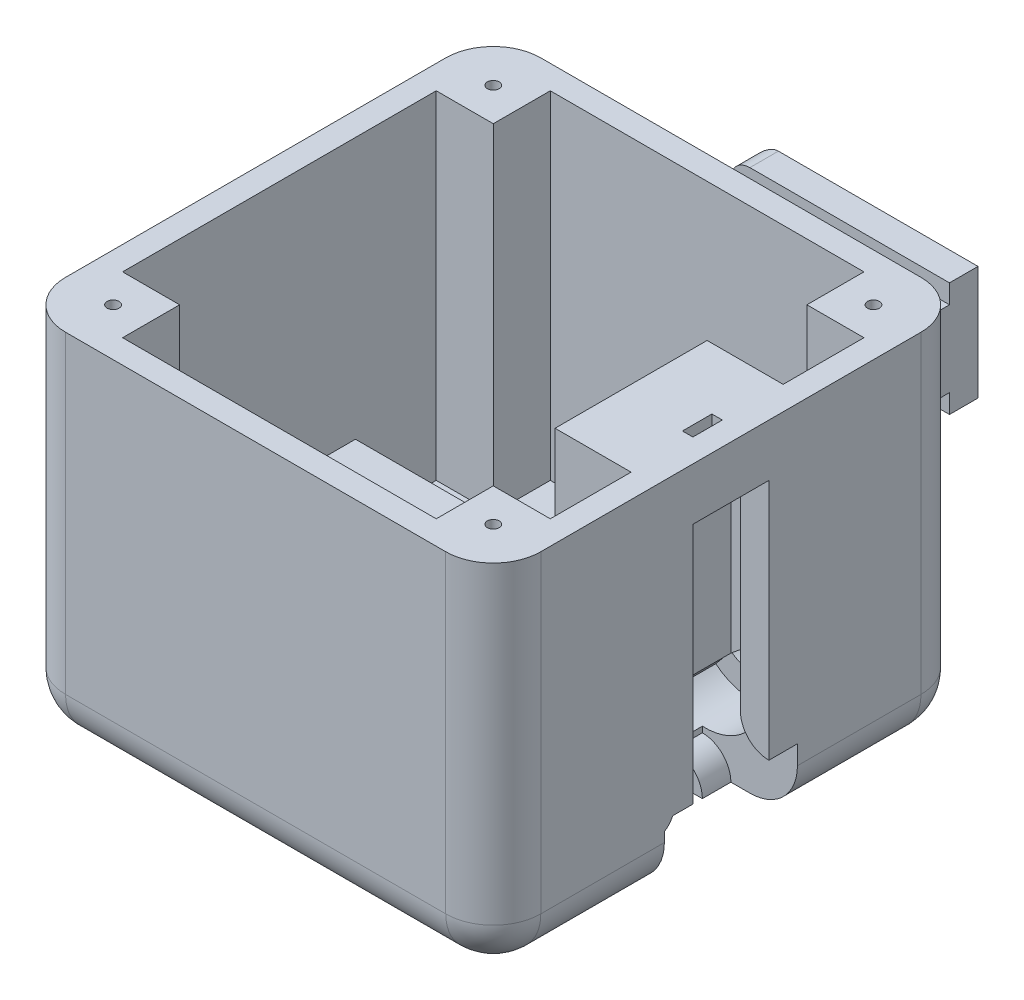
SolidWorks part; units mm, degrees
ref_plane "Front Plane" through (0, 0, 0) normal (0, 0, 1) x (1, 0, 0)
ref_plane "Top Plane" through (0, 0, 0) normal (0, 1, 0) x (1, 0, 0)
ref_plane "Right Plane" through (0, 0, 0) normal (1, 0, 0) x (0, 0, -1)
sketch "Sketch1" plane through (0, 0, 0) normal (0, 1, 0) x (1, 0, 0)
  line L1 (25, 25) -> (-25, 25)
  line L2 (25, 25) -> (25, -25)
  line L3 (25, -25) -> (-25, -25)
  line L4 (-25, 25) -> (-25, -25)
  line L5 (25, 25) -> (-25, -25) construction
  line L6 (25, -25) -> (-25, 25) construction
  point P0 (0, 0)
  dimension "D1" = 50
  dimension "D2" = 50
extrude "Boss-Extrude1" add sketch "Sketch1" along normal blind 38
shell "Shell1" thickness 2.5 removed face at (0, 38, 0)
sketch "Sketch2" plane through (0, 2.5, 0) normal (0, 1, 0) x (1, 0, 0)
  line L2 (9.676, 17.0496) -> (9.676, 13.5) construction
  line L3 (-10.3, -16.9504) -> (-10.324, -16.9504) construction
  line L4 (-10.324, 9.8396) -> (-10.324, -13.6) construction
  line L5 (-10.3, 6.5) -> (-10.324, 6.5)
  line L13 (10.3, 13.5) -> (10.3, 22.5)
  line L14 (22.5, 7.28) -> (22.5, 22.5)
  line L15 (10.3, 7.28) -> (22.5, 7.28)
  line L16 (10.3, 7.28) -> (10.3, 13.5)
  line L17 (10.3, 13.5) -> (9.676, 13.5)
  line L19 (22.5, 22.5) -> (10.3, 22.5)
  line L28 (-10.3, -13.6) -> (-10.324, -13.6)
  line L29 (-10.3, -16.9504) -> (-10.3, -20.79)
  line L35 (9.676, -16.9504) -> (-10.3, -16.9504) construction
  line L40 (22.5, -22.5) -> (22.5, 22.5) construction
  point P0 (0, 0)
  line M21 (22.5, -22.5) -> (22.5, 22.5)
  line M22 (22.5, 22.5) -> (-22.5, 22.5)
  dimension "D7" = 9
sketch "Sketch3" plane through (0, 2.5, 0) normal (0, 1, 0) x (1, 0, 0)
  line L0 (22.5, -8) -> (22.5, 8)
  line L1 (22.5, -22.5) -> (22.5, 22.5) construction
  line L2 (22.5, 8) -> (22.5, -8)
  line L3 (22.5, 8) -> (-22.5, 8)
  line L4 (22.5, -8) -> (-22.5, -8)
  line L5 (-22.5, 8) -> (-22.5, -8)
  line L6 (-22.5, 22.5) -> (-22.5, -22.5) construction
  point P4 (22.5, 0)
  point P6 (22.5, 0)
  line M6 (-22.5, 22.5) -> (-22.5, -22.5)
  line M8 (22.5, -22.5) -> (22.5, 22.5)
  dimension "D1" = 16
extrude "Boss-Extrude2" add sketch "Sketch2" along normal blind 21 contours L16 L15 L13 M21 M22
extrude "Boss-Extrude3" add sketch "Sketch3" along normal blind 8 contours L4 L3 M8 M6
sketch "Sketch4" plane through (0, 0, 0) normal (0, -1, 0) x (1, 0, 0)
  line L4 (25, -4) -> (-7.5, -4)
  line L5 (22.5, -8) -> (25, -8) construction
  line L6 (22.5, 8) -> (25, 8) construction
  line L7 (22.5, 0) -> (25, 0)
  line L8 (25, 25) -> (25, -25) construction
  line L9 (-7.5, -4) -> (-7.5, 4)
  line L10 (-7.5, 4) -> (25, 4)
  line L11 (25, 4) -> (25, -4)
  point P10 (25, 0)
  dimension "D1" = 8
  dimension "D2" = 32.5
extrude "Cut-Extrude1" cut sketch "Sketch4" against normal blind 3
ref_plane "Plane1" through (0, 3, 0) normal (0, -1, 0) x (-1, 0, 0)
sketch "Sketch7" plane through (0, 3, 0) normal (0, -1, 0) x (-1, 0, 0)
  line L5 (-25, 4) -> (-25, -4) construction
  line L6 (-25, -6) -> (-25, 6)
  line L7 (-25, -6) -> (7.5, -6)
  line L8 (-25, 6) -> (7.5, 6)
  line L9 (7.5, -6) -> (7.5, 6)
  line L10 (-25, -25) -> (-25, -4) construction
  line L11 (-25, 4) -> (-25, 25) construction
  point P4 (-25, 0)
  point P11 (-25, 0)
  dimension "D1" = 12
  dimension "D2" = 32.5
extrude "Cut-Extrude2" cut sketch "Sketch7" against normal blind 3
sketch "Sketch8" plane through (22.5, 0, 0) normal (-1, 0, 0) x (0, 0, 1)
  line L0 (-8, 10.5) -> (-8, 38)
  line L1 (22.5, 38) -> (-22.5, 38) construction
  line L2 (8, 10.5) -> (8, 38)
  line L3 (8, 38) -> (-8, 38)
  line L4 (-8, 10.5) -> (8, 10.5)
extrude "Boss-Extrude4" add sketch "Sketch8" along normal blind 8
sketch "Sketch9" plane through (25, 0, 0) normal (1, 0, 0) x (0, 0, -1)
  line L0 (-4, 0) -> (-4, 32.5)
  line L2 (4, 0) -> (4, 32.5)
  line L3 (4, 32.5) -> (-4, 32.5)
  line L4 (-4, 0) -> (4, 0)
  dimension "D1" = 32.5
extrude "Cut-Extrude3" cut sketch "Sketch9" against normal blind 3 contours L4 L2 L3 L0
ref_plane "Plane2" through (22, 0, 0) normal (1, 0, 0) x (0, 0, -1)
sketch "Sketch10" plane through (22, 0, 0) normal (1, 0, 0) x (0, 0, -1)
  line L0 (-6, 0) -> (-6, 32.5)
  line L1 (-25, 0) -> (-4, 0) construction
  line L3 (6, 3) -> (6, 0)
  line L4 (4, 0) -> (25, 0) construction
  line L5 (6, 0) -> (6, 32.5)
  line L7 (6, 32.5) -> (-6, 32.5)
  line L8 (-6, 0) -> (6, 0)
  dimension "D1" = 32.5
extrude "Cut-Extrude5" cut sketch "Sketch10" against normal blind 3 contours L0 L8 L3 L5 L7
ref_plane "Plane3" through (0, 0, 4) normal (0, 0, -1) x (-1, 0, 0)
sketch "Sketch13" plane through (0, 0, 4) normal (0, 0, -1) x (-1, 0, 0)
  line L0 (-25, 0) -> (-22, 0)
  line L1 (-25, 0) -> (-25, 3.0115)
  line L2 (-22, 0) -> (-22, 3.0115)
  line L3 (-25, 3.0115) -> (-22, 3.0115)
extrude "Cut-Extrude7" cut sketch "Sketch13" against normal blind 2 and the other way blind 10
ref_plane "Plane4" through (0, 0, 6) normal (0, 0, -1) x (-1, 0, 0)
fillet "Fillet1" radius 5 9 edges at (-25, 19, 25) (25, 19, 25) (25, 19, -25) (-25, 19, -25) (-25, 0, 0) (0, 0, 25) (25, 0, 15.5) (0, 0, -25) (25, 0, -15.5)
ref_plane "Plane6" through (0, 0, 1.5) normal (0, 0, -1) x (-1, 0, 0)
sketch "Sketch16" plane through (0, 0, 1.5) normal (0, 0, -1) x (-1, 0, 0)
  line L0 (-25, 9.7) -> (-25, 0) construction
  line L1 (-17.1, 9.7) -> (-15.3, 9.7) construction
  line L2 (-25, 0) -> (-15.3, 0) construction
  line L3 (-15.3, 9.7) -> (-15.3, 7.9) construction
  line L5 (-15.3, 7.9) -> (-15.3, 0) construction
  line L6 (-25, 9.7) -> (-17.1, 9.7) construction
  circle A0 centre (-15.3, 9.7) radius 1.8
  dimension "D3" = 3.6
  dimension "D1" = 9.7
  dimension "D2" = 9.7
extrude "Cut-Extrude8" cut sketch "Sketch16" along normal through all
sketch "Sketch17" plane through (0, 0, -25) normal (0, 0, -1) x (-1, 0, 0)
  line L0 (-20, 36) -> (3, 36)
  line L1 (-20, 38) -> (-20, 5) construction
  line L2 (3, 36) -> (3, 24)
  line L3 (3, 24) -> (-20, 24)
  line L4 (-20, 24) -> (-20, 36)
  line L5 (-20, 38) -> (20, 38) construction
  dimension "D1" = 12
  dimension "D2" = 23
  dimension "D3" = 2
extrude "Boss-Extrude5" add sketch "Sketch17" along normal blind 6
sketch "Sketch18" plane through (-3, 0, 0) normal (-1, 0, 0) x (0, 0, 1)
  line L0 (-31, 30) -> (-25, 30) construction
  line L1 (-31, 24) -> (-31, 36) construction
  line L2 (-25, 24) -> (-25, 36) construction
  line L3 (-28, 24) -> (-25, 24)
  line L4 (-28, 24) -> (-28, 26)
  line L5 (-25, 24) -> (-25, 26)
  line L6 (-28, 26) -> (-25, 26)
  line L7 (-31, 24) -> (-25, 24) construction
  line L8 (-25, 36) -> (-25, 34)
  line L9 (-28, 34) -> (-25, 34)
  line L10 (-28, 36) -> (-28, 34)
  line L11 (-28, 36) -> (-25, 36)
  dimension "D1" = 4
extrude "Cut-Extrude9" cut sketch "Sketch18" against normal through all
ref_plane "Plane5" through (0, 0, -25) normal (0, 0, -1) x (-1, 0, 0)
sketch "Sketch20" plane through (0, 0, 4) normal (0, 0, -1) x (-1, 0, 0)
  line L0 (-22, 6) -> (-22, 32.5) construction
  line L2 (-22, 10) -> (-22, 7)
  line L7 (-22, 6) -> (-25, 6) construction
  line L8 (-24, 6) -> (-22, 6)
  line L9 (-22, 6) -> (-22, 7)
  line L10 (-24, 6) -> (-25, 6)
  line L11 (-25, 6) -> (-25, 7)
  line L12 (-25, 6) -> (-25, 32.5) construction
  arc A0 (-25, 7) -> (-22, 10) centre (-25, 10) ccw
  dimension "D1" = 1
  dimension "D2" = 3
extrude "Cut-Extrude12" cut sketch "Sketch20" against normal blind 2
sketch "Sketch21" plane through (0, 0, 4) normal (0, 0, -1) x (-1, 0, 0)
  line L4 (-19, 3) -> (-19, 0)
  line L5 (-19, 0) -> (-18, 0)
  line L6 (7.5, 0) -> (-19, 0) construction
  line L7 (-19, 3) -> (-15, 3)
  line L8 (7.5, 3) -> (-19, 3) construction
  arc A3 (-18, 0) -> (-15, 3) centre (-15, 0) cw
  dimension "D1" = 4
  dimension "D2" = 1
extrude "Cut-Extrude13" cut sketch "Sketch21" against normal blind 2
sketch "Sketch22" plane through (0, 0, 4) normal (0, 0, -1) x (-1, 0, 0)
  line L1 (-15.3, 9.7) -> (-11.4116, 5)
  line L2 (-19, 6) -> (7.5, 6) construction
  line L3 (-15.3, 9.7) -> (-20, 13.5884)
  line L4 (-19, 6) -> (-19, 32.5) construction
  arc A0 (-20, 13.5884) -> (-11.4116, 5) centre (-15.3, 9.7) ccw
  arc A1 (-11.4116, 5) -> (-20, 13.5884) centre (-15.3, 9.7) ccw construction
  dimension "D1" = 12.2
  dimension "D2" = 1
  dimension "D3" = 1
extrude "Cut-Extrude14" cut sketch "Sketch22" along normal blind 16
sketch "Sketch19" plane through (0, 0, -25) normal (0, 0, -1) x (-1, 0, 0)
  line L5 (-29.1876, 23.5876) -> (-2.7229, -2.8771) construction
  line L6 (-8.2477, 16.7523) -> (-36.3257, -11.3257) construction
  line L18 (-13.6992, 10.523) -> (-13.1688, 11.0533)
  line L19 (-13.1688, 11.0533) -> (-13.9467, 11.8312)
  line L20 (-13.9467, 11.8312) -> (-14.477, 11.3008)
  line L21 (-17.4312, 8.3467) -> (-16.9008, 8.877)
  line L22 (-16.6533, 7.5688) -> (-17.4312, 8.3467)
  line L23 (-16.123, 8.0992) -> (-16.6533, 7.5688)
  arc A4 (-13.6992, 10.523) -> (-14.477, 11.3008) centre (-15.3, 9.7) ccw
  arc A5 (-16.123, 8.0992) -> (-16.9008, 8.877) centre (-15.3, 9.7) cw
  circle A6 centre (-15.3, 9.7) radius 1.8
  circle A7 centre (-15.3, 9.7) radius 1.8 construction
  point P6 (-13.434, 10.7882)
  dimension "D1" = 3.6
  dimension "D3" = 0.75
  dimension "D2" = 1.1
extrude "Cut-Extrude10" cut sketch "Sketch19" against normal blind 19.5 contours A6 L21 L22 L23 | A6 L18 L19 L20
sketch "Sketch23" [suppressed] plane through (0, 0, 6) normal (0, 0, -1) x (-1, 0, 0)
  line L0 (-15.3, 9.7) -> (-18.1679, 13.7958)
  line L1 (-15.3, 9.7) -> (-11.2042, 6.8321)
  line L2 (-15.3, 9.7) -> (-18.8355, 6.1645) construction
  line L4 (-18.275, 13.9488) -> (-18.1679, 13.7958)
  circle A0 centre (-15.3, 9.7) radius 5
  arc A1 (-11.2042, 6.8321) -> (-18.8355, 6.1645) centre (-15.3, 9.7) cw
  arc A2 (-14.477, 11.3008) -> (-16.9008, 8.877) centre (-15.3, 9.7) ccw construction
  arc A3 (-11.2042, 6.8321) -> (-18.5504, 5.9006) centre (-15.3, 9.7) ccw
  dimension "D1" = 10
  dimension "D2" = 200
  dimension "D3" = 100
fillet "Fillet4" radius 2 3 edges at (-3, 36, -29.5) (-3, 24, -29.5) (-3, 30, -31)
sketch "Sketch26" plane through (0, 0, 6) normal (0, 0, -1) x (-1, 0, 0)
  line L0 (-25, 6) -> (-25, 0)
  line L1 (-25, 0) -> (-19, 0)
  line L2 (-19, 0) -> (-19, 6)
  line L3 (-19, 6) -> (-25, 6)
  dimension "D1" = 6
  dimension "D2" = 6
extrude "Cut-Extrude18" cut sketch "Sketch26" against normal blind 1 and the other way blind 13
fillet "Fillet7" [suppressed] radius 2
sketch "Sketch29" plane through (0, 0, 6) normal (0, 0, -1) x (-1, 0, 0)
  line L0 (-16.4991, 10.692) -> (-15.3054, 9.6393)
  line L1 (-15.3054, 9.6393) -> (-14.2582, 8.4407)
  line L2 (-12.2389, 6) -> (-15.3, 9.7) construction
  line L3 (-15.3, 9.7) -> (-19, 12.7611) construction
  arc A0 (-16.4991, 10.692) -> (-14.2582, 8.4407) centre (-15.3054, 9.6393) cw
extrude "Boss-Extrude6" add sketch "Sketch29" along normal blind 4.5
sketch "Sketch30" plane through (-7.5, 0, 0) normal (1, 0, 0) x (0, 0, -1)
  line L0 (-4, 3) -> (4, 3) construction
  line L2 (-2.17, 3.9) -> (2.17, 3.9)
  line L3 (-2.17, 3.9) -> (-2.17, 2.1)
  line L4 (-2.17, 2.1) -> (2.17, 2.1)
  line L5 (2.17, 3.9) -> (2.17, 2.1)
  line L6 (-2.17, 3.9) -> (2.17, 2.1) construction
  line L7 (-2.17, 2.1) -> (2.17, 3.9) construction
  point P4 (0, 3)
  point P5 (0, 3)
  dimension "D1" = 4.34
  dimension "D2" = 1.8
extrude "Cut-Extrude19" cut sketch "Sketch30" against normal blind 4.4 contours L3 L2 L5 L4
sketch "Sketch31" plane through (0, 32.5, 0) normal (0, -1, 0) x (1, 0, 0)
  line L0 (22, 4) -> (22, -4) construction
  line L2 (21.1, 2.17) -> (22.9, 2.17)
  line L3 (21.1, 2.17) -> (21.1, -2.17)
  line L4 (21.1, -2.17) -> (22.9, -2.17)
  line L5 (22.9, 2.17) -> (22.9, -2.17)
  line L6 (21.1, 2.17) -> (22.9, -2.17) construction
  line L7 (21.1, -2.17) -> (22.9, 2.17) construction
  point P4 (22, 0)
  point P5 (22, 0)
  dimension "D1" = 4.34
  dimension "D2" = 1.8
extrude "Cut-Extrude20" cut sketch "Sketch31" against normal blind 4.4
sketch "Sketch32" plane through (0, 36.9, 0) normal (0, -1, 0) x (1, 0, 0)
  line L0 (22, -2.17) -> (22, 2.17) construction
  line L1 (21.1, -2.17) -> (22.9, -2.17) construction
  line L2 (22.9, 2.17) -> (21.1, 2.17) construction
  line L4 (21.45, 1.55) -> (22.55, 1.55)
  line L5 (21.45, 1.55) -> (21.45, -1.55)
  line L6 (21.45, -1.55) -> (22.55, -1.55)
  line L7 (22.55, 1.55) -> (22.55, -1.55)
  line L8 (21.45, 1.55) -> (22.55, -1.55) construction
  line L9 (21.45, -1.55) -> (22.55, 1.55) construction
  point P6 (22, 0)
  point P7 (22, 0)
  dimension "D1" = 3.1
  dimension "D2" = 1.1
extrude "Cut-Extrude21" cut sketch "Sketch32" against normal through all
sketch "Sketch33" plane through (-11.9, 0, 0) normal (1, 0, 0) x (0, 0, -1)
  line L0 (-2.17, 3) -> (2.17, 3) construction
  line L1 (-2.17, 3.9) -> (-2.17, 2.1) construction
  line L2 (2.17, 3.9) -> (2.17, 2.1) construction
  line L4 (1.55, 3.55) -> (-1.55, 3.55)
  line L5 (1.55, 3.55) -> (1.55, 2.45)
  line L6 (1.55, 2.45) -> (-1.55, 2.45)
  line L7 (-1.55, 3.55) -> (-1.55, 2.45)
  line L8 (1.55, 3.55) -> (-1.55, 2.45) construction
  line L9 (1.55, 2.45) -> (-1.55, 3.55) construction
  point P6 (0, 3)
  point P7 (0, 3)
  dimension "D1" = 3.1
  dimension "D2" = 1.1
extrude "Cut-Extrude22" cut sketch "Sketch33" against normal blind 3.55
sketch "Sketch34" plane through (0, 10.5, 0) normal (0, 1, 0) x (1, 0, 0)
  line L0 (-22.5, 0) -> (-14.45, 0)
  line L3 (-15.45, 1.55) -> (-13.45, 1.55)
  line L4 (-15.45, 1.55) -> (-15.45, -1.55)
  line L5 (-15.45, -1.55) -> (-13.45, -1.55)
  line L6 (-13.45, 1.55) -> (-13.45, -1.55)
  line L7 (-15.45, 1.55) -> (-13.45, -1.55) construction
  line L8 (-15.45, -1.55) -> (-13.45, 1.55) construction
  dimension "D1" = 8.05
  dimension "D2" = 3.1
  dimension "D3" = 2
  dimension "D4" = 8
extrude "Cut-Extrude23" cut sketch "Sketch34" against normal blind 7.3
sketch "Sketch35" [suppressed] plane through (0, 2.5, 0) normal (0, 1, 0) x (1, 0, 0)
  line L0 (-10.3, 13.5) -> (-10.3, 8)
  line L1 (-10.3, 13.5) -> (-5.3, 13.5)
  line L2 (-10.3, 8) -> (-5.3, 8)
  line L3 (-5.3, 13.5) -> (-5.3, 8)
  line L4 (0, 8) -> (0, 13.2497) construction
  line L5 (10.3, 8) -> (-10.3, 8) construction
  line L6 (10.3, 8) -> (5.3, 8)
  line L7 (5.3, 13.5) -> (5.3, 8)
  line L8 (10.3, 13.5) -> (5.3, 13.5)
  line L9 (10.3, 13.5) -> (10.3, 8)
  line M6 (-10.3, 8) -> (10.3, 8)
  line M7 (10.3, 8) -> (10.3, 13.5)
  line M8 (10.3, 13.5) -> (-10.3, 13.5)
  dimension "D1" = 5
extrude "Boss-Extrude7" [suppressed] add sketch "Sketch35" along normal blind 8 contours L7 M8 M6 M7 | L3 L2 L0 L1
sketch "Sketch36" [suppressed] plane through (0, 2.5, 0) normal (0, 1, 0) x (1, 0, 0)
  line L0 (-10.3, -20.79) -> (-10.3, -15.79)
  line L1 (-10.3, -20.79) -> (-5.3, -20.79)
  line L2 (-10.3, -15.79) -> (-5.3, -15.79)
  line L3 (-5.3, -20.79) -> (-5.3, -15.79)
  line L4 (0, -20.79) -> (0, -14.6562) construction
  line L5 (10.3, -15.79) -> (5.3, -15.79)
  line L6 (5.3, -20.79) -> (5.3, -15.79)
  line L7 (10.3, -20.79) -> (5.3, -20.79)
  line L8 (10.3, -20.79) -> (10.3, -15.79)
  line L9 (-10.3, -13.6) -> (-10.3, -20.79) construction
  line L10 (10.3, -20.79) -> (-10.3, -20.79) construction
  point P18 (0, -20.79)
  dimension "D1" = 5
  dimension "D2" = 5
extrude "Boss-Extrude8" [suppressed] add sketch "Sketch36" along normal blind 8
sketch3d "3DSketch1" [suppressed]
  line L0 (-10.3, 10.5, -6.5) -> (-10.3, 10.5, -13.5) construction
  line L1 (10.3, 10.5, -13.5) -> (5.3, 10.5, -13.5) construction
  circle A0 centre (-8.3, 10.5, -11.5) radius 1.2131
  circle A1 centre (8.3, 10.5, -11.5) radius 1.0739
  point P2 (-8.3, 11.7131, -11.5)
  point P7 (8.3, 11.5739, -11.5)
  dimension "D1" = 2
  dimension "D2" = 2
  dimension "D3" = 2
  dimension "D4" = 2
hole_wizard "CSK SLOT for M2 Countersunk Flat Head Screw1" [suppressed] positions "Sketch37" profile "Sketch39" size "M2" standard "ISO"
sketch "Sketch37" [suppressed] plane through (0, 0, 0) normal (0, -1, 0) x (-1, 0, 0)
  point P0 (-8.3, 11.5)
  point P4 (8.3, 11.5)
sketch "Sketch39" plane through (8.3, 0, -11.5) normal (1, 0, 0) x (0, 0, -1)
  line L0 (0, 0) -> (0, 11.221)
  line L1 (0, 11.221) -> (1.2, 10.5)
  line L2 (1.2, 10.5) -> (1.2, 9.5)
  line L3 (1.2, 9.5) -> (2.2, 8.5)
  line L4 (2.2, 8.5) -> (2.2, 0)
  line L6 (2.2, 0) -> (0, 0)
  line L7 (-1.2, 9.5) -> (-2.2, 8.5) construction
  line L10 (0, 11.221) -> (-1.2, 10.5) construction
  line L11 (0, -6.35) -> (0, 107.95) construction
  dimension "Hole Dia." = 2.4
  dimension "Hole Depth" = 10.5
  dimension "C'Sink Dia." = 4.4
  dimension "C'Sink Angle" = 90
  dimension "Drill Angle" = 118
  dimension "Head Clearance" = 8.5
sketch3d "3DSketch2" [suppressed]
  circle A0 centre (-8.3, 10.5, 18.79) radius 1.3639
  circle A1 centre (8.3, 10.5, 18.79) radius 1.8762
  point P2 (-8.3, 11.8639, 18.79)
  point P5 (8.3, 12.3762, 18.79)
  dimension "D1" = 2
  dimension "D2" = 2
  dimension "D3" = 2
  dimension "D4" = 2
hole_wizard "CSK SLOT for M2 Countersunk Flat Head Screw2" [suppressed] positions "Sketch40" profile "Sketch41" size "M2" standard "ISO"
sketch "Sketch40" [suppressed] plane through (0, 0, 0) normal (0, -1, 0) x (-1, 0, 0)
  point P0 (-8.3, -18.79)
  point P3 (8.3, -18.79)
sketch "Sketch41" plane through (8.3, 0, 18.79) normal (1, 0, 0) x (0, 0, -1)
  line L0 (0, 0) -> (0, 11.221)
  line L1 (0, 11.221) -> (1.2, 10.5)
  line L2 (1.2, 10.5) -> (1.2, 9.5)
  line L3 (1.2, 9.5) -> (2.2, 8.5)
  line L4 (2.2, 8.5) -> (2.2, 0)
  line L6 (2.2, 0) -> (0, 0)
  line L7 (-1.2, 9.5) -> (-2.2, 8.5) construction
  line L10 (0, 11.221) -> (-1.2, 10.5) construction
  line L11 (0, -6.35) -> (0, 107.95) construction
  dimension "Hole Dia." = 2.4
  dimension "Hole Depth" = 10.5
  dimension "C'Sink Dia." = 4.4
  dimension "C'Sink Angle" = 90
  dimension "Drill Angle" = 118
  dimension "Head Clearance" = 8.5
sketch "Sketch44" plane through (0, 0, 4) normal (0, 0, -1) x (-1, 0, 0)
  line L0 (-19, 12.7611) -> (-19, 6)
  line L1 (-19, 6) -> (-12.2389, 6)
  line L4 (-19, 12.7611) -> (-16.4991, 10.692)
  line L5 (-16.4991, 10.692) -> (-15.3054, 9.6393)
  line L6 (-15.3054, 9.6393) -> (-14.2582, 8.4407)
  line L7 (-14.2582, 8.4407) -> (-12.2389, 6)
extrude "Cut-Extrude26" [suppressed] cut sketch "Sketch44" against normal blind 2
sketch "Sketch45" plane through (0, 0, 1.5) normal (0, 0, -1) x (-1, 0, 0)
  line L0 (-17.0423, 7.9577) -> (-13.5577, 11.4423) construction
  line L1 (-16.6533, 7.5688) -> (-17.4312, 8.3467) construction
  line L2 (-13.1688, 11.0533) -> (-13.9467, 11.8312) construction
  line L3 (-16.5728, 10.9728) -> (-14.0272, 8.4272) construction
  circle A0 centre (-15.3, 9.7) radius 3.575
  circle A4 centre (-15.3, 9.7) radius 1.8 construction
  circle A5 centre (-15.3, 9.7) radius 1.8 construction
  point P21 (-15.3, 9.7)
  dimension "D1" = 7.15
extrude "Cut-Extrude27" cut sketch "Sketch45" along normal blind 20
ref_plane "Plane7" through (0, 0, -6) normal (0, 0, 1) x (1, 0, 0)
sketch "Sketch46" plane through (0, 0, -6) normal (0, 0, 1) x (1, 0, 0)
  line L0 (20.1497, 6) -> (22, 6)
  line L1 (20.1497, 6) -> (20.1497, 10)
  line L2 (22, 6) -> (22, 10)
  line L3 (20.1497, 10) -> (22, 10)
  line L4 (19, 3) -> (19, 4.8503)
  line L5 (19, 3) -> (15, 3)
  line L6 (19, 4.8503) -> (15, 4.8503)
  line L7 (15, 3) -> (15, 4.8503)
  dimension "D1" = 4
  dimension "D2" = 4
extrude "Cut-Extrude28" cut sketch "Sketch46" against normal blind 1
sketch "Sketch43" plane through (0, 0, -4) normal (0, 0, 1) x (1, 0, 0)
  line L0 (19, 0) -> (18, 0)
  line L1 (19, 0) -> (-7.5, 0) construction
  line L2 (19, 0) -> (19, 3)
  line L3 (19, 3) -> (15, 3)
  line L4 (19, 3) -> (-7.5, 3) construction
  arc A1 (18, 0) -> (15, 3) centre (15, 0) ccw
  dimension "D1" = 1
  dimension "D2" = 4
extrude "Cut-Extrude25" cut sketch "Sketch43" against normal blind 3
sketch "Sketch42" plane through (0, 0, -4) normal (0, 0, 1) x (1, 0, 0)
  line L0 (22, 6) -> (25, 6)
  line L1 (25, 6) -> (25, 7)
  line L2 (25, 6) -> (25, 32.5) construction
  line L3 (22, 6) -> (22, 10)
  line L4 (22, 6) -> (22, 32.5) construction
  arc A1 (25, 7) -> (22, 10) centre (25, 10) cw
  dimension "D1" = 4
  dimension "D2" = 1
extrude "Cut-Extrude24" cut sketch "Sketch42" against normal blind 3
sketch "Sketch47" plane through (0, 0, 4) normal (0, 0, -1) x (-1, 0, 0)
  line L0 (-19, 12.7611) -> (-16.4991, 10.692)
  line L1 (-16.4991, 10.692) -> (-15.3054, 9.6393)
  line L2 (-15.3054, 9.6393) -> (-14.2582, 8.4407)
  line L3 (-14.2582, 8.4407) -> (-12.2389, 6)
  line L4 (-12.2389, 6) -> (-19, 6)
  line L5 (-19, 6) -> (-19, 12.7611)
extrude "Cut-Extrude29" cut sketch "Sketch47" against normal blind 2
fillet "Fillet8" radius 2 2 edges at (19, 3, 6) (22, 6, 6)
fillet "Fillet9" [suppressed] radius 2
sketch "Sketch48" plane through (0, 0, -7.28) normal (0, 0, 1) x (1, 0, 0)
  line L0 (10.3, 10.5) -> (10.3, 23.5)
  line L1 (10.3, 23.5) -> (14.5, 23.5)
  line L2 (14.5, 23.5) -> (14.5, 13.1843)
  line L4 (10.3, 10.5) -> (11.8157, 10.5)
  line L6 (10.3, 23.5) -> (14.5, 23.5) construction
  line L7 (14.5, 13.1843) -> (14.5, 23.5) construction
  arc A6 (11.8157, 10.5) -> (14.5, 13.1843) centre (15.5761, 9.4239) cw
extrude "Boss-Extrude9" add sketch "Sketch48" along normal up to vertex (8.78 mm away) up to point (14.5, 11.0121, 1.5)
ref_plane "Plane8" through (0, 0, 1.5) normal (0, 0, 1) x (1, 0, 0)
sketch "Sketch49" plane through (0, 0, 1.5) normal (0, 0, 1) x (1, 0, 0)
  line L0 (14.5, 13.1843) -> (14.5, 23.5) construction
  line L1 (10.3, 23.5) -> (14.5, 23.5)
  line L2 (10.3, 23.5) -> (10.3, 10.5)
  line L3 (10.3, 10.5) -> (14.5, 10.5)
  line L4 (14.5, 23.5) -> (14.5, 10.5)
  line L5 (13.9666, 10.5) -> (11.8157, 10.5) construction
extrude "Boss-Extrude10" add sketch "Sketch49" along normal up to vertex (6.5 mm away) up to point (14.5, 10.5, 8)
ref_plane "Plane9" through (0, 2.5, 0) normal (0, 1, 0) x (1, 0, 0)
sketch "Sketch50" plane through (0, 2.5, 0) normal (0, 1, 0) x (1, 0, 0)
  line L0 (-22.5, 22.5) -> (-16.5, 22.5)
  line L1 (-22.5, -22.5) -> (-16.5, -22.5)
  line L2 (-22.5, -22.5) -> (-22.5, -16.5)
  line L3 (-22.5, -16.5) -> (-16.5, -16.5)
  line L4 (-16.5, -22.5) -> (-16.5, -16.5)
  line L5 (-22.5, 22.5) -> (-22.5, 16.5)
  line L6 (-22.5, 16.5) -> (-16.5, 16.5)
  line L7 (-16.5, 22.5) -> (-16.5, 16.5)
  line L8 (22.5, 22.5) -> (22.5, 16.5)
  line L9 (22.5, 22.5) -> (16.5, 22.5)
  line L10 (16.5, 22.5) -> (16.5, 16.5)
  line L11 (22.5, 16.5) -> (16.5, 16.5)
  line L12 (22.5, -22.5) -> (16.5, -22.5)
  line L13 (22.5, -22.5) -> (22.5, -16.5)
  line L14 (22.5, -16.5) -> (16.5, -16.5)
  line L15 (16.5, -22.5) -> (16.5, -16.5)
  point P20 (0, 0)
  dimension "D1" = 6
  dimension "D2" = 6
  dimension "D3" = 4
extrude "Boss-Extrude11" add sketch "Sketch50" along normal up to surface (35.5 mm away) up to face at (22, 38, 0)
hole_wizard "M1.6 Tapped Hole1" positions "Sketch51" profile "Sketch52" tap size "M1.6" standard "ISO"
sketch "Sketch51" plane through (0, 38, 0) normal (0, 1, 0) x (1, 0, 0)
  line L0 (-25, 20) -> (-25, -20) construction
  line L1 (-20, -25) -> (20, -25) construction
  point P0 (-20, -20)
  point P11 (-20, 20)
  point P12 (20, 20)
  point P13 (20, -20)
  dimension "D1" = 5
  dimension "D2" = 5
  dimension "D3" = 4
sketch "Sketch52" plane through (-20, 38, 20) normal (1, 0, 0) x (0, 0, 1)
  line L0 (0, 0) -> (0, 5.3755)
  line L1 (0, 5.3755) -> (0.625, 5)
  line L2 (0.625, 5) -> (0.625, 0)
  line L5 (0.625, 0) -> (0, 0)
  line L10 (0, 5.3755) -> (-0.625, 5) construction
  line L11 (0, -6.35) -> (0, 107.95) construction
  dimension "Tap Drill Dia." = 1.25
  dimension "Tap Drill Depth" = 5
  dimension "Drill Angle" = 118
cosmetic thread "Hole Thread1" parameters "D1"=3.2, "D2"=1.6
cosmetic thread "Hole Thread2" parameters "D1"=3.2, "D2"=1.6
cosmetic thread "Hole Thread3" parameters "D1"=3.2, "D2"=1.6
cosmetic thread "Hole Thread4" parameters "D1"=3.2, "D2"=1.6
